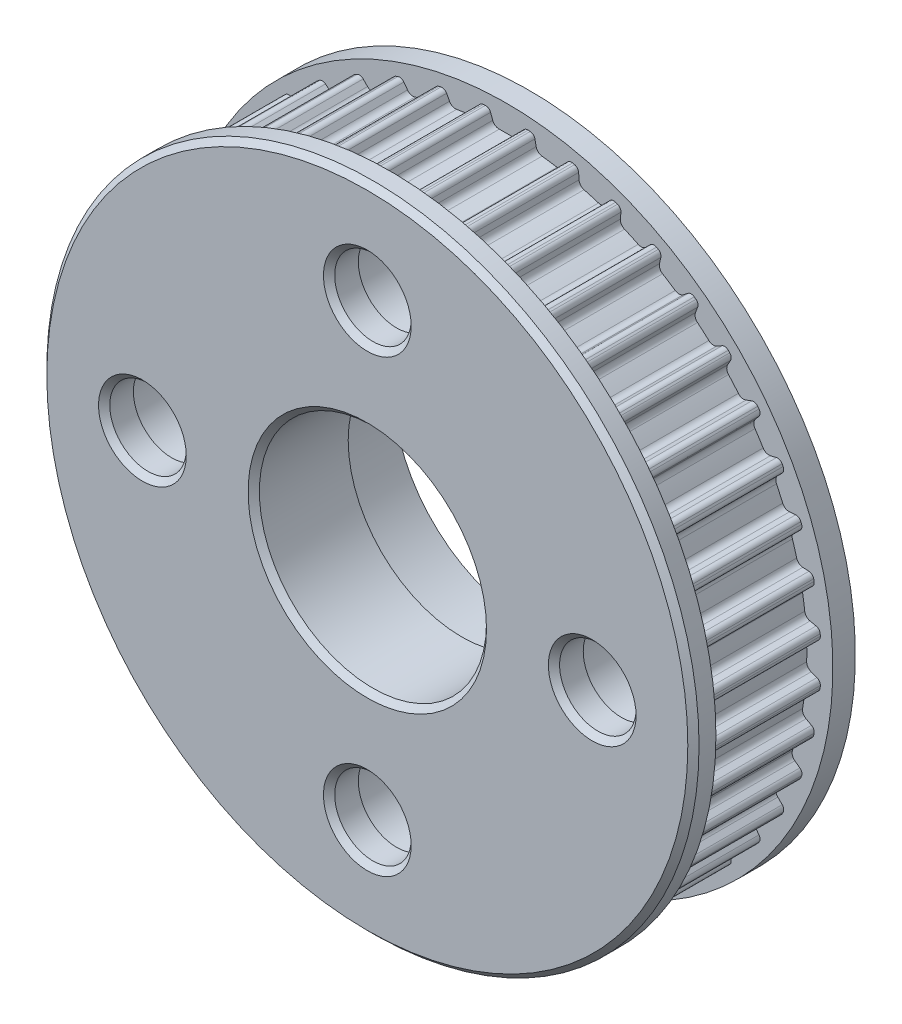
SolidWorks part; units mm, degrees
ref_plane "正面" through (0, 0, 0) normal (0, 0, 1) x (1, 0, 0)
ref_plane "平面" through (0, 0, 0) normal (0, 1, 0) x (1, 0, 0)
ref_plane "右側面" through (0, 0, 0) normal (1, 0, 0) x (0, 0, -1)
sketch "ｽｹｯﾁ1" plane through (0, 0, 0) normal (0, 0, 1) x (1, 0, 0)
  line L0 (-0.7186, 13.7918) -> (-0.6244, 13.5331)
  line L1 (0.6244, 13.5331) -> (0.7186, 13.7918)
  line L2 (0, 0) -> (0, 25.6447) construction
  line L3 (-0.335, 13.3358) -> (0.335, 13.3358) construction
  line L4 (-0.997, 13.9394) -> (0, 0) construction
  line L5 (0, 0) -> (0.997, 13.9394) construction
  line L6 (-0.997, 13.9394) -> (-0.7134, 9.9745)
  line L7 (0.7134, 9.9745) -> (0.997, 13.9394)
  arc A0 (-0.335, 13.3358) -> (0.335, 13.3358) centre (0, 0) cw
  arc A1 (0.9504, 13.9426) -> (0.997, 13.9394) centre (0, 0) cw
  arc A2 (-0.9504, 13.9426) -> (-0.997, 13.9394) centre (0, 0) ccw
  arc A3 (-0.335, 13.3358) -> (-0.6244, 13.5331) centre (-0.3425, 13.6357) cw
  arc A4 (-0.7186, 13.7918) -> (-0.9504, 13.9426) centre (-0.9347, 13.7132) ccw
  arc A5 (0.7186, 13.7918) -> (0.9504, 13.9426) centre (0.9347, 13.7132) cw
  arc A6 (0.335, 13.3358) -> (0.6244, 13.5331) centre (0.3425, 13.6357) ccw
  arc A7 (-0.7134, 9.9745) -> (0.7134, 9.9745) centre (0, 0) ccw
  dimension "D3" = 0.23
  dimension "D4" = 13.975
  dimension "D5" = 0.3
  dimension "D6" = 13.34
  dimension "D10" = 10
  dimension "D1" = 20
  dimension "D2" = 20
  dimension "D7" = 0.67
  dimension "D8" = 4.091
  dimension "D9" = 8.182
extrude "ﾎﾞｽ - 押し出し1" add sketch "ｽｹｯﾁ1" along normal blind 5.2
pattern_circular "円形ﾊﾟﾀｰﾝ1" count 44 over 360 about axis through (0, 0, 5.2) along (0, 0, -1) of "ﾎﾞｽ - 押し出し1"
sketch "ｽｹｯﾁ2" plane through (0, 0, 0) normal (0, 0, -1) x (-1, 0, 0)
  circle A0 centre (0, 0) radius 14.5
  dimension "D1" = 29
extrude "ﾎﾞｽ - 押し出し2" add sketch "ｽｹｯﾁ2" along normal blind 1
sketch "ｽｹｯﾁ3" plane through (0, 0, 5.2) normal (0, 0, 1) x (1, 0, 0)
  circle A0 centre (0, 0) radius 14.5
  circle A1 centre (0, 0) radius 14.5 construction
extrude "ﾎﾞｽ - 押し出し3" add sketch "ｽｹｯﾁ3" along normal blind 1
sketch "ｽｹｯﾁ4" plane through (0, 0, 6.2) normal (0, 0, 1) x (1, 0, 0)
  line L0 (0, 10) -> (0, 0) construction
  line L1 (10, 0) -> (0, 0) construction
  line L2 (0, -10) -> (0, 0) construction
  line L3 (-10, 0) -> (0, 0) construction
  circle A0 centre (0, 10) radius 1.7
  circle A1 centre (10, 0) radius 1.7
  circle A2 centre (0, -10) radius 1.7
  circle A3 centre (-10, 0) radius 1.7
  circle A4 centre (0, 0) radius 5.05
  point P13 (0, 0)
  dimension "D1" = 3.4
  dimension "D4" = 10.1
  dimension "D2" = 10
  dimension "D3" = 4
extrude "ｶｯﾄ - 押し出し1" cut sketch "ｽｹｯﾁ4" against normal through all
sketch "ｽｹｯﾁ5" plane through (0, 0, -1) normal (0, 0, -1) x (-1, 0, 0)
  circle A0 centre (0, 0) radius 6.05
  dimension "D1" = 12.1
extrude "ｶｯﾄ - 押し出し2" cut sketch "ｽｹｯﾁ5" against normal blind 3
sketch "ｽｹｯﾁ6" plane through (0, 0, -1) normal (0, 0, -1) x (-1, 0, 0)
  circle A0 centre (0, 10) radius 2.01
  circle A1 centre (10, 0) radius 2.01
  circle A2 centre (0, -10) radius 2.01
  circle A3 centre (-10, 0) radius 2.01
  point P11 (0, 0)
  dimension "D1" = 4.02
  dimension "D2" = 4
extrude "ｶｯﾄ - 押し出し3" cut sketch "ｽｹｯﾁ6" against normal blind 5.9
chamfer "面取り1" distance 0.25 angle 45 6 edges at (14.5, 0, 6.2) (5.05, 0, 6.2) (11.7, 0, 6.2) (1.7, -10, 6.2) (-8.3, 0, 6.2) (1.7, 10, 6.2)
